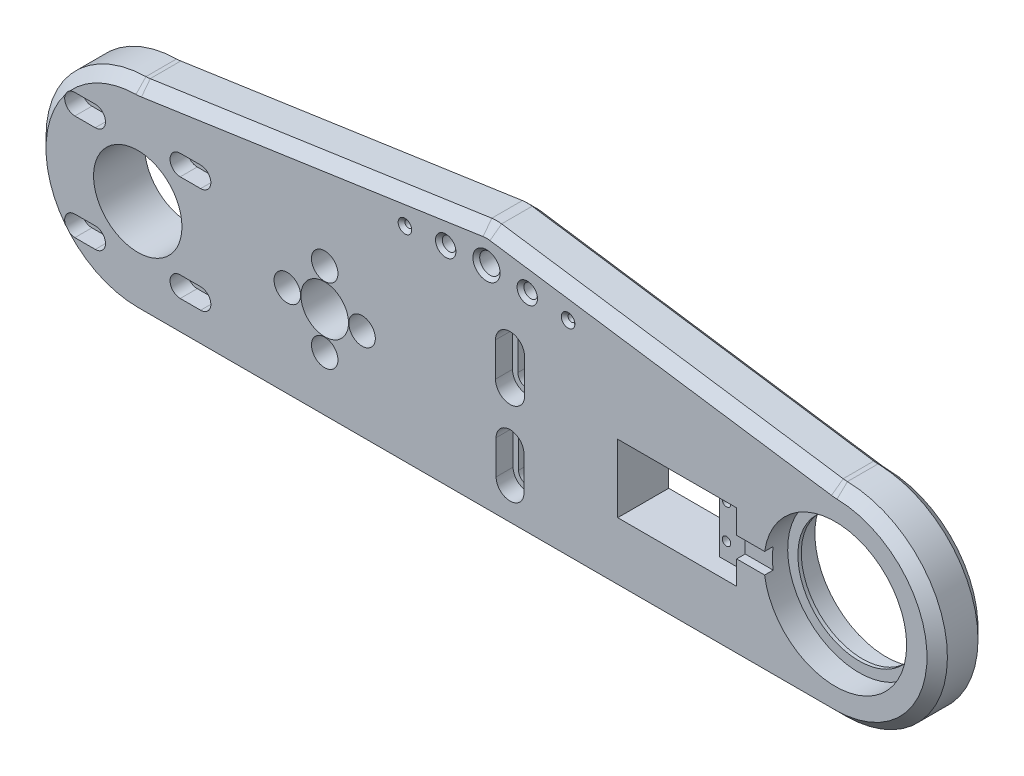
SolidWorks part; units mm, degrees
material "PLA+"
ref_plane "Front Plane" through (0, 0, 0) normal (0, 0, 1) x (1, 0, 0)
ref_plane "Top Plane" through (0, 0, 0) normal (0, 1, 0) x (1, 0, 0)
ref_plane "Right Plane" through (0, 0, 0) normal (1, 0, 0) x (0, 0, -1)
sketch "Sketch2" plane through (0, 0, 0) normal (0, 0, 1) x (1, 0, 0)
  line L0 (176.22, -10) -> (176.22, 10)
  line L2 (166.22, 10) -> (166.22, -10)
  line L4 (0, -30) -> (205.22, -30)
  line L5 (205.22, 30) -> (0, 30)
  line L6 (141.22, -10) -> (141.22, 10)
  line L7 (141.22, -10) -> (176.22, -10)
  line L8 (176.22, 10) -> (141.22, 10)
  line L9 (205.22, 0) -> (0, 0) construction
  line L10 (109.0063, 18) -> (109.0063, -17.8029) construction
  line L11 (-15.5, -15.5) -> (15.5, -15.5) construction
  line L12 (-15.5, -15.5) -> (-15.5, 15.5) construction
  line L13 (-15.5, 15.5) -> (15.5, 15.5) construction
  line L14 (15.5, -15.5) -> (15.5, 15.5) construction
  line L15 (-15.5, -15.5) -> (15.5, 15.5) construction
  line L16 (-15.5, 15.5) -> (15.5, -15.5) construction
  line L17 (106.8485, 22.3123) -> (106.8485, 7.3123)
  line L18 (112.224, 22.3123) -> (112.224, 9.6993)
  line L19 (109.5363, 25) -> (109.5363, 30) construction
  line L20 (106.5063, -7.5) -> (106.5063, -22.5)
  line L21 (111.5063, -7.5) -> (111.5063, -22.5)
  line L22 (109.0063, -30) -> (109.0063, -25) construction
  circle A0 centre (205.22, 0) radius 21
  circle A8 centre (66, 0) radius 2.25
  circle A9 centre (55, -11) radius 2.25
  circle A10 centre (44, 0) radius 2.25
  circle A11 centre (55, 11) radius 2.25
  circle A12 centre (55, 0) radius 7
  circle A13 centre (0, 0) radius 13
  circle A14 centre (15.5, 15.5) radius 1.5
  circle A15 centre (15.5, -15.5) radius 1.5
  circle A16 centre (-15.5, -15.5) radius 1.5
  circle A17 centre (-15.5, 15.5) radius 1.5
  circle A19 centre (168.22, 5) radius 1.25
  circle A20 centre (205.22, 0) radius 17
  circle A21 centre (55, 0) radius 11 construction
  circle A22 centre (168.22, -5) radius 1.25
  arc A25 (205.22, 30) -> (205.22, -30) centre (205.22, 0) cw
  arc A26 (0, 30) -> (0, -30) centre (0, 0) ccw
  arc A27 (112.224, 22.3123) -> (106.8485, 22.3123) centre (109.5363, 22.3123) ccw
  arc A28 (106.8485, 7.3123) -> (112.224, 9.6993) centre (109.0063, 9.6993) ccw
  arc A29 (106.5063, -22.5) -> (111.5063, -22.5) centre (109.0063, -22.5) ccw
  arc A30 (111.5063, -7.5) -> (106.5063, -7.5) centre (109.0063, -7.5) ccw
  dimension "D1" = 26
  dimension "D3" = 31
  dimension "D4" = 42
  dimension "D7" = 3
  dimension "D8" = 14
  dimension "D9" = 4.5
  dimension "D10" = 15
  dimension "D11" = 5
  dimension "D12" = 5
  dimension "D13" = 2.5
  dimension "D15" = 4
  dimension "D20" = 29
  dimension "D23" = 150.22
  dimension "D25" = 22
  dimension "D21" = 35.8029
  dimension "D5" = 10
  dimension "D6" = 35
  dimension "D14" = 8
  dimension "D16" = 5
  dimension "D17" = 20
  dimension "D18" = 18
  dimension "D19" = 205.22
  dimension "D22" = 15
  dimension "D24" = 31
sketch "Sketch3" plane through (0, 0, 0) normal (0, 0, 1) x (1, 0, 0)
  line L0 (141.22, -10) -> (176.22, -10) construction
  line L1 (141.22, -10) -> (141.22, 10) construction
  line L2 (176.22, -10) -> (176.22, 10) construction
  line L3 (176.22, 10) -> (141.22, 10) construction
  line L4 (0, -30) -> (205.22, -30) construction
  line L5 (205.22, 30) -> (0, 30) construction
  line L6 (141.22, -10) -> (176.22, -10)
  line L7 (141.22, -10) -> (141.22, 10)
  line L8 (176.22, -10) -> (176.22, 10)
  line L9 (176.22, 10) -> (141.22, 10)
  line L10 (0, -30) -> (205.22, -30)
  line L11 (205.22, 30) -> (0, 30)
  line L12 (-18.5, 15.5) -> (-12.5, 15.5) construction
  line L13 (-18.5, 17.3) -> (-12.5, 17.3)
  line L14 (-18.5, 13.7) -> (-12.5, 13.7)
  line L15 (12.5, 15.5) -> (18.5, 15.5) construction
  line L16 (12.5, 17.3) -> (18.5, 17.3)
  line L17 (12.5, 13.7) -> (18.5, 13.7)
  line L18 (-18.5, -15.5) -> (-12.5, -15.5) construction
  line L19 (-18.5, -13.7) -> (-12.5, -13.7)
  line L20 (-18.5, -17.3) -> (-12.5, -17.3)
  line L21 (12.5, -15.5) -> (18.5, -15.5) construction
  line L22 (12.5, -13.7) -> (18.5, -13.7)
  line L23 (12.5, -17.3) -> (18.5, -17.3)
  arc A0 (-18.5, 17.3) -> (-18.5, 13.7) centre (-18.5, 15.5) ccw
  arc A1 (-12.5, 13.7) -> (-12.5, 17.3) centre (-12.5, 15.5) ccw
  arc A2 (12.5, 17.3) -> (12.5, 13.7) centre (12.5, 15.5) ccw
  arc A3 (18.5, 13.7) -> (18.5, 17.3) centre (18.5, 15.5) ccw
  arc A4 (-18.5, -13.7) -> (-18.5, -17.3) centre (-18.5, -15.5) ccw
  circle A5 centre (55, -11) radius 2.25 construction
  circle A6 centre (66, 0) radius 2.25 construction
  circle A7 centre (44, 0) radius 2.25 construction
  circle A8 centre (55, 0) radius 7 construction
  circle A9 centre (55, 11) radius 2.25 construction
  circle A10 centre (-15.5, 15.5) radius 1.5 construction
  circle A11 centre (-15.5, -15.5) radius 1.5 construction
  circle A12 centre (15.5, -15.5) radius 1.5 construction
  circle A13 centre (15.5, 15.5) radius 1.5 construction
  circle A14 centre (0, 0) radius 13 construction
  circle A15 centre (205.22, 0) radius 21 construction
  arc A16 (205.22, -30) -> (205.22, 30) centre (205.22, 0) ccw construction
  arc A17 (0, 30) -> (0, -30) centre (0, 0) ccw construction
  circle A23 centre (55, -11) radius 2.25
  circle A24 centre (66, 0) radius 2.25
  circle A25 centre (44, 0) radius 2.25
  circle A26 centre (55, 0) radius 7
  circle A27 centre (55, 11) radius 2.25
  circle A28 centre (-15.5, 15.5) radius 1.5 construction
  circle A29 centre (-15.5, -15.5) radius 1.5 construction
  circle A30 centre (15.5, -15.5) radius 1.5 construction
  circle A31 centre (15.5, 15.5) radius 1.5 construction
  circle A32 centre (0, 0) radius 13
  circle A33 centre (205.22, 0) radius 21
  arc A34 (205.22, -30) -> (205.22, 30) centre (205.22, 0) ccw
  arc A35 (0, 30) -> (0, -30) centre (0, 0) ccw
  arc A36 (-12.5, -17.3) -> (-12.5, -13.7) centre (-12.5, -15.5) ccw
  arc A37 (12.5, -13.7) -> (12.5, -17.3) centre (12.5, -15.5) ccw
  arc A38 (18.5, -17.3) -> (18.5, -13.7) centre (18.5, -15.5) ccw
  point P0 (-15.5, 15.5)
  point P3 (-15.5, 15.5)
  point P8 (15.5, 15.5)
  point P34 (15.5, 15.5)
  point P59 (-15.5, -15.5)
  point P62 (-15.5, -15.5)
  point P67 (15.5, -15.5)
  point P70 (15.5, -15.5)
extrude "Boss-Extrude1" add sketch "Sketch3" along normal mid plane 15
sketch "Sketch4" plane through (0, 0, 0) normal (0, 0, 1) x (1, 0, 0)
  circle A0 centre (205.22, 0) radius 21 construction
  circle A2 centre (205.22, 0) radius 21
  circle A4 centre (205.22, 0) radius 18
  dimension "D1" = 36
extrude "Boss-Extrude2" add sketch "Sketch4" along normal mid plane 1
sketch "Sketch5" plane through (0, 0, 0) normal (0, 0, 1) x (1, 0, 0)
  line L0 (176.22, -10) -> (176.22, 10) construction
  line L1 (166.22, 10) -> (166.22, -10) construction
  line L2 (176.22, -10) -> (176.22, 10)
  line L3 (166.22, 10) -> (166.22, -10)
  line L4 (166.22, 10) -> (176.22, 10)
  line L5 (166.22, -10) -> (176.22, -10)
  circle A0 centre (168.22, -5) radius 1.25 construction
  circle A1 centre (168.22, 5) radius 1.25 construction
  circle A2 centre (168.22, -5) radius 1.25
  circle A3 centre (168.22, 5) radius 1.25
extrude "Boss-Extrude3" add sketch "Sketch5" along normal mid plane 5
sketch "Sketch6" plane through (0, 0, 0) normal (0, 0, 1) x (1, 0, 0)
  line L0 (0, 30) -> (102.61, 45)
  line L1 (102.61, 45) -> (205.22, 30)
  line L2 (205.22, 30) -> (0, 30)
  line L3 (102.61, 31) -> (78.61, 31) construction
  line L4 (102.61, 45) -> (102.61, 35) construction
  line L5 (205.22, 30) -> (0, 30) construction
  circle A0 centre (102.61, 35) radius 4
  circle A1 centre (90.61, 34) radius 3
  circle A2 centre (78.61, 33) radius 2
  circle A3 centre (114.61, 34) radius 3
  circle A4 centre (126.61, 33) radius 2
  point P15 (102.61, 30)
  dimension "D2" = 8
  dimension "D3" = 6
  dimension "D4" = 4
  dimension "D1" = 15
  dimension "D5" = 12
  dimension "D6" = 12
  dimension "D7" = 10
extrude "Boss-Extrude4" add sketch "Sketch6" along normal mid plane 15 contours A2 | L2 L1 L0 A3 A2 A1 A0 A4 | A1 | A4 | A3 | A0 region at (51.6026, 35.464, 0) region at (102.61, 35, 0) region at (90.61, 34, 0) region at (78.61, 33, 0) region at (114.61, 34, 0) region at (126.61, 33, 0)
fillet "Fillet1" radius 10 3 edges at (205.22, 30, 0) (102.61, 45, 0) (0, 30, 0)
sketch "Sketch7" plane through (0, 0, 7.5) normal (0, 0, 1) x (1, 0, 0)
  circle A0 centre (126.61, 33) radius 2 construction
  circle A1 centre (114.61, 34) radius 3 construction
  circle A2 centre (102.61, 35) radius 4 construction
  circle A3 centre (90.61, 34) radius 3 construction
  circle A4 centre (78.61, 33) radius 2 construction
  circle A5 centre (126.61, 33) radius 2
  circle A6 centre (114.61, 34) radius 3
  circle A7 centre (102.61, 35) radius 4
  circle A8 centre (90.61, 34) radius 3
  circle A9 centre (78.61, 33) radius 2
extrude "Cut-Extrude1" cut sketch "Sketch7" against normal blind 1
chamfer "Chamfer1" distance 1 angle 45 5 edges at (128.61, 33, 6.5) (117.61, 34, 6.5) (106.61, 35, 6.5) (93.61, 34, 6.5) (80.61, 33, 6.5)
mirror "Mirror1" about plane through (0, 0, 0) normal (0, 0, 1) of "Chamfer1", "Cut-Extrude1"
chamfer "Chamfer2" distance 3 angle 45 16 edges at (154.3045, 37.4431, -7.5) (102.61, 44.8937, -7.5) (50.9155, 37.4431, -7.5) (154.3045, 37.4431, 7.5) (102.61, 44.8937, 7.5) (50.9155, 37.4431, 7.5) (205.1767, 30.0263, -7.5) (0.0433, 30.0263, -7.5) (235.2186, -0.2921, -7.5) (102.61, -30, -7.5) (-29.9986, -0.2921, -7.5) (205.1767, 30.0263, 7.5) (0.0433, 30.0263, 7.5) (235.2186, -0.2921, 7.5) (102.61, -30, 7.5) (-29.9986, -0.2921, 7.5)
sketch "Sketch9" plane through (0, 0, 7.5) normal (0, 0, 1) x (1, 0, 0)
  line L4 (141.75, -10) -> (141.75, 10) construction
  line L8 (109.5363, 18) -> (109.5363, -17.8029) construction
  line L9 (141.75, 0) -> (109.5363, 0) construction
  line L15 (106.8485, 17.3123) -> (106.8485, 7.3123)
  line L16 (112.224, 17.3123) -> (112.224, 7.3123)
  line L18 (107.0363, -7.5) -> (107.0363, -17.5)
  line L19 (112.0363, -7.5) -> (112.0363, -17.5)
  arc A17 (112.224, 17.3123) -> (106.8485, 17.3123) centre (109.5363, 17.3123) ccw
  arc A18 (106.8485, 7.3123) -> (112.224, 7.3123) centre (109.5363, 7.3123) ccw
  arc A19 (107.0363, -17.5) -> (112.0363, -17.5) centre (109.5363, -17.5) ccw
  arc A20 (112.0363, -7.5) -> (107.0363, -7.5) centre (109.5363, -7.5) ccw
  dimension "D18" = 20
  dimension "D19" = 10
  dimension "D20" = 35.8029
  dimension "D23" = 10
extrude "Cut-Extrude2" cut sketch "Sketch9" against normal through all
sketch "Sketch10" plane through (0, 0, 7.5) normal (0, 0, 1) x (1, 0, 0)
  circle A0 centre (102.61, 35) radius 3
  circle A1 centre (114.61, 34) radius 2
  circle A2 centre (90.61, 34) radius 2
  circle A3 centre (126.61, 33) radius 1
  circle A4 centre (78.61, 33) radius 1
extrude "Cut-Extrude3" cut sketch "Sketch10" against normal through all
sketch "Sketch19" plane through (0, 0, 7.5) normal (0, 0, 1) x (1, 0, 0)
  line L0 (-18.5, 17.3) -> (-12.5, 17.3)
  line L1 (-18.5, 13.7) -> (-12.5, 13.7)
  line L2 (12.5, 17.3) -> (18.5, 17.3)
  line L3 (12.5, 13.7) -> (18.5, 13.7)
  line L4 (-18.5, -13.7) -> (-12.5, -13.7)
  line L5 (-18.5, -17.3) -> (-12.5, -17.3)
  line L6 (12.5, -13.7) -> (18.5, -13.7)
  line L7 (12.5, -17.3) -> (18.5, -17.3)
  line L8 (-18.5, 18.5) -> (-12.5, 18.5)
  line L9 (-18.5, 12.5) -> (-12.5, 12.5)
  line L10 (12.5, 12.5) -> (18.5, 12.5)
  line L11 (12.5, 18.5) -> (18.5, 18.5)
  line L12 (-18.5, -18.5) -> (-12.5, -18.5)
  line L13 (-18.5, -12.5) -> (-12.5, -12.5)
  line L14 (12.5, -18.5) -> (18.5, -18.5)
  line L15 (12.5, -12.5) -> (18.5, -12.5)
  arc A0 (-18.5, 17.3) -> (-18.5, 13.7) centre (-18.5, 15.5) ccw
  arc A1 (-12.5, 13.7) -> (-12.5, 17.3) centre (-12.5, 15.5) ccw
  arc A2 (12.5, 17.3) -> (12.5, 13.7) centre (12.5, 15.5) ccw
  arc A3 (18.5, 13.7) -> (18.5, 17.3) centre (18.5, 15.5) ccw
  arc A4 (-18.5, -13.7) -> (-18.5, -17.3) centre (-18.5, -15.5) ccw
  arc A5 (-12.5, -17.3) -> (-12.5, -13.7) centre (-12.5, -15.5) ccw
  arc A6 (12.5, -13.7) -> (12.5, -17.3) centre (12.5, -15.5) ccw
  arc A7 (18.5, -17.3) -> (18.5, -13.7) centre (18.5, -15.5) ccw
  arc A8 (-12.5, 12.5) -> (-12.5, 18.5) centre (-12.5, 15.5) ccw
  arc A9 (-18.5, 18.5) -> (-18.5, 12.5) centre (-18.5, 15.5) ccw
  arc A10 (12.5, 18.5) -> (12.5, 12.5) centre (12.5, 15.5) ccw
  arc A11 (18.5, 12.5) -> (18.5, 18.5) centre (18.5, 15.5) ccw
  arc A12 (-18.5, -12.5) -> (-18.5, -18.5) centre (-18.5, -15.5) ccw
  arc A13 (-12.5, -18.5) -> (-12.5, -12.5) centre (-12.5, -15.5) ccw
  arc A14 (12.5, -12.5) -> (12.5, -18.5) centre (12.5, -15.5) ccw
  arc A15 (18.5, -18.5) -> (18.5, -12.5) centre (18.5, -15.5) ccw
  dimension "D1" = 1.2
extrude "Cut-Extrude4" cut sketch "Sketch19" against normal blind 5
sketch "Sketch20" plane through (0, 0, -7.5) normal (0, 0, -1) x (-1, 0, 0)
  line L10 (-18.5, 17.3) -> (-12.5, 17.3)
  line L11 (-18.5, 13.7) -> (-12.5, 13.7)
  line L12 (12.5, 17.3) -> (18.5, 17.3)
  line L13 (12.5, 13.7) -> (18.5, 13.7)
  line L14 (-18.5, -13.7) -> (-12.5, -13.7)
  line L15 (-18.5, -17.3) -> (-12.5, -17.3)
  line L16 (12.5, -13.7) -> (18.5, -13.7)
  line L17 (12.5, -17.3) -> (18.5, -17.3)
  line L18 (-18.5, 12.5) -> (-12.5, 12.5)
  line L19 (-18.5, 18.5) -> (-12.5, 18.5)
  line L20 (12.5, 12.5) -> (18.5, 12.5)
  line L21 (12.5, 18.5) -> (18.5, 18.5)
  line L22 (-18.5, -12.5) -> (-12.5, -12.5)
  line L23 (-18.5, -18.5) -> (-12.5, -18.5)
  line L24 (12.5, -18.5) -> (18.5, -18.5)
  line L25 (12.5, -12.5) -> (18.5, -12.5)
  arc A10 (-18.5, 17.3) -> (-18.5, 13.7) centre (-18.5, 15.5) ccw
  arc A11 (-12.5, 13.7) -> (-12.5, 17.3) centre (-12.5, 15.5) ccw
  arc A12 (12.5, 17.3) -> (12.5, 13.7) centre (12.5, 15.5) ccw
  arc A13 (18.5, 13.7) -> (18.5, 17.3) centre (18.5, 15.5) ccw
  arc A14 (-18.5, -13.7) -> (-18.5, -17.3) centre (-18.5, -15.5) ccw
  arc A15 (-12.5, -17.3) -> (-12.5, -13.7) centre (-12.5, -15.5) ccw
  arc A16 (12.5, -13.7) -> (12.5, -17.3) centre (12.5, -15.5) ccw
  arc A17 (18.5, -17.3) -> (18.5, -13.7) centre (18.5, -15.5) ccw
  arc A18 (-18.5, 18.5) -> (-18.5, 12.5) centre (-18.5, 15.5) ccw
  arc A19 (-12.5, 12.5) -> (-12.5, 18.5) centre (-12.5, 15.5) ccw
  arc A20 (12.5, 18.5) -> (12.5, 12.5) centre (12.5, 15.5) ccw
  arc A21 (18.5, 12.5) -> (18.5, 18.5) centre (18.5, 15.5) ccw
  arc A22 (-12.5, -18.5) -> (-12.5, -12.5) centre (-12.5, -15.5) ccw
  arc A23 (-18.5, -12.5) -> (-18.5, -18.5) centre (-18.5, -15.5) ccw
  arc A24 (12.5, -12.5) -> (12.5, -18.5) centre (12.5, -15.5) ccw
  arc A25 (18.5, -18.5) -> (18.5, -12.5) centre (18.5, -15.5) ccw
  dimension "D1" = 1.2
extrude "Cut-Extrude5" cut sketch "Sketch20" against normal blind 5
sketch "Sketch21" plane through (0, 0, 7.5) normal (0, 0, 1) x (1, 0, 0)
  circle A8 centre (55, 11) radius 3.9
  circle A9 centre (55, -11) radius 3.9
  circle A10 centre (44, 0) radius 3.9
  circle A11 centre (66, 0) radius 3.9
  dimension "D1" = 7.8
  dimension "D2" = 7.8
  dimension "D3" = 7.8
  dimension "D4" = 7.8
extrude "Cut-Extrude6" cut sketch "Sketch21" against normal blind 6
sketch "Sketch22" plane through (0, 0, -7.5) normal (0, 0, -1) x (-1, 0, 0)
  circle A0 centre (-55, 11) radius 3.9
  circle A1 centre (-55, -11) radius 3.9
  circle A2 centre (-44, 0) radius 3.9
  circle A3 centre (-66, 0) radius 3.9
  dimension "D1" = 7.8
  dimension "D2" = 7.8
  dimension "D3" = 7.8
  dimension "D4" = 7.8
extrude "Cut-Extrude7" cut sketch "Sketch22" against normal blind 6
sketch "Sketch23" plane through (0, 0, 7.5) normal (0, 0, 1) x (1, 0, 0)
  line L7 (113.6363, -17.5) -> (113.6363, -7.5)
  line L8 (105.4363, -7.5) -> (105.4363, -17.5)
  line L9 (113.6363, -17.5) -> (113.6363, -7.5)
  line L10 (105.4363, -7.5) -> (105.4363, -17.5)
  line L14 (-18.5, -14.5) -> (-12.5, -14.5)
  line L15 (-12.5, -16.5) -> (-18.5, -16.5)
  line L16 (0, -29) -> (205.22, -29)
  line L17 (204.4078, 29.1081) -> (103.9118, 43.7991)
  line L18 (101.3082, 43.7991) -> (0.8122, 29.1081)
  line L19 (-18.5, 16.5) -> (-12.5, 16.5)
  line L20 (-12.5, 14.5) -> (-18.5, 14.5)
  line L21 (-18.5, -14.5) -> (-12.5, -14.5)
  line L22 (-12.5, -16.5) -> (-18.5, -16.5)
  line L23 (0, -29) -> (205.22, -29)
  line L24 (204.4078, 29.1081) -> (103.9118, 43.7991)
  line L25 (101.3082, 43.7991) -> (0.8122, 29.1081)
  line L26 (-18.5, 16.5) -> (-12.5, 16.5)
  line L27 (-12.5, 14.5) -> (-18.5, 14.5)
  line L28 (105.2485, 17.3123) -> (105.2485, 7.3123)
  line L29 (113.824, 7.3123) -> (113.824, 17.3123)
  line L30 (105.2485, 17.3123) -> (105.2485, 7.3123)
  line L31 (113.824, 7.3123) -> (113.824, 17.3123)
  arc A7 (105.4363, -17.5) -> (113.6363, -17.5) centre (109.5363, -17.5) ccw
  arc A8 (113.6363, -7.5) -> (105.4363, -7.5) centre (109.5363, -7.5) ccw
  arc A9 (105.4363, -17.5) -> (113.6363, -17.5) centre (109.5363, -17.5) ccw
  arc A10 (113.6363, -7.5) -> (105.4363, -7.5) centre (109.5363, -7.5) ccw
  arc A20 (105.2485, 7.3123) -> (113.824, 7.3123) centre (109.5363, 7.3123) ccw
  arc A21 (113.824, 17.3123) -> (105.2485, 17.3123) centre (109.5363, 17.3123) ccw
  arc A22 (105.2485, 7.3123) -> (113.824, 7.3123) centre (109.5363, 7.3123) ccw
  arc A23 (113.824, 17.3123) -> (105.2485, 17.3123) centre (109.5363, 17.3123) ccw
  arc A26 (-18.5, -14.5) -> (-18.5, -16.5) centre (-18.5, -15.5) ccw
  arc A27 (-12.5, -16.5) -> (-12.5, -14.5) centre (-12.5, -15.5) ccw
  arc A28 (205.22, -29) -> (205.7847, 28.9945) centre (205.22, 0) ccw
  arc A29 (204.4078, 29.1081) -> (205.7847, 28.9945) centre (205.9989, 39.9924) ccw
  arc A30 (103.9118, 43.7991) -> (101.3082, 43.7991) centre (102.61, 34.8937) ccw
  arc A31 (-0.5647, 28.9945) -> (0.8122, 29.1081) centre (-0.7789, 39.9924) ccw
  arc A32 (-18.5, 16.5) -> (-18.5, 14.5) centre (-18.5, 15.5) ccw
  arc A33 (-12.5, 14.5) -> (-12.5, 16.5) centre (-12.5, 15.5) ccw
  arc A34 (-0.5647, 28.9945) -> (0, -29) centre (0, 0) ccw
  arc A35 (-18.5, -14.5) -> (-18.5, -16.5) centre (-18.5, -15.5) ccw
  arc A36 (-12.5, -16.5) -> (-12.5, -14.5) centre (-12.5, -15.5) ccw
  arc A37 (205.22, -29) -> (205.7847, 28.9945) centre (205.22, 0) ccw
  arc A38 (204.4078, 29.1081) -> (205.7847, 28.9945) centre (205.9989, 39.9924) ccw
  arc A39 (103.9118, 43.7991) -> (101.3082, 43.7991) centre (102.61, 34.8937) ccw
  arc A40 (-0.5647, 28.9945) -> (0.8122, 29.1081) centre (-0.7789, 39.9924) ccw
  arc A41 (-18.5, 16.5) -> (-18.5, 14.5) centre (-18.5, 15.5) ccw
  arc A42 (-12.5, 14.5) -> (-12.5, 16.5) centre (-12.5, 15.5) ccw
  arc A43 (-0.5647, 28.9945) -> (0, -29) centre (0, 0) ccw
  dimension "D1" = 2
  dimension "D2" = 1.6
  dimension "D3" = 1.6
extrude "Cut-Extrude10" cut sketch "Sketch23" against normal blind 5 contours L31 A23 L30 A22 | L9 A10 L10 A9 region at (109.5363, -12.5, 7.5) region at (109.5363, 12.3123, 7.5)
sketch "Sketch25" plane through (0, 0, -7.5) normal (0, 0, -1) x (-1, 0, 0)
  line L14 (-113.824, 17.3123) -> (-113.824, 7.3123)
  line L15 (-105.2485, 7.3123) -> (-105.2485, 17.3123)
  line L16 (-113.824, 17.3123) -> (-113.824, 7.3123)
  line L17 (-105.2485, 7.3123) -> (-105.2485, 17.3123)
  line L23 (-113.6363, -7.5) -> (-113.6363, -17.5)
  line L24 (-105.4363, -17.5) -> (-105.4363, -7.5)
  line L25 (-113.6363, -7.5) -> (-113.6363, -17.5)
  line L26 (-105.4363, -17.5) -> (-105.4363, -7.5)
  arc A20 (-113.824, 7.3123) -> (-105.2485, 7.3123) centre (-109.5363, 7.3123) ccw
  arc A21 (-105.2485, 17.3123) -> (-113.824, 17.3123) centre (-109.5363, 17.3123) ccw
  arc A22 (-113.824, 7.3123) -> (-105.2485, 7.3123) centre (-109.5363, 7.3123) ccw
  arc A23 (-105.2485, 17.3123) -> (-113.824, 17.3123) centre (-109.5363, 17.3123) ccw
  arc A29 (-113.6363, -17.5) -> (-105.4363, -17.5) centre (-109.5363, -17.5) ccw
  arc A30 (-105.4363, -7.5) -> (-113.6363, -7.5) centre (-109.5363, -7.5) ccw
  arc A31 (-113.6363, -17.5) -> (-105.4363, -17.5) centre (-109.5363, -17.5) ccw
  arc A32 (-105.4363, -7.5) -> (-113.6363, -7.5) centre (-109.5363, -7.5) ccw
  dimension "D1" = 1.6
  dimension "D2" = 1.6
extrude "Cut-Extrude11" cut sketch "Sketch25" against normal blind 5
sketch "Sketch27" plane through (0, 0, -7.5) normal (0, 0, -1) x (-1, 0, 0)
  line L0 (0, 0) -> (-23.8, 0) construction
  circle A0 centre (-23.8, 0) radius 2.59
  dimension "D2" = 5.18
  dimension "D1" = 23.8
extrude "Cut-Extrude13" cut sketch "Sketch27" against normal blind 3
sketch "Sketch28" plane through (0, 0, 7.5) normal (0, 0, 1) x (1, 0, 0)
  line L0 (141.22, 0) -> (179.6819, 0) construction
  line L1 (141.22, 10) -> (141.22, -10) construction
  line L2 (176.22, -10) -> (176.22, 10) construction
  line L3 (176.22, 3) -> (185.22, 3)
  line L4 (176.22, 3) -> (176.22, -3)
  line L5 (176.22, -3) -> (185.22, -3)
  line L6 (185.22, 3) -> (185.22, -3)
  dimension "D1" = 3
  dimension "D2" = 3
  dimension "D3" = 9
extrude "Cut-Extrude14" cut sketch "Sketch28" against normal blind 2.5
